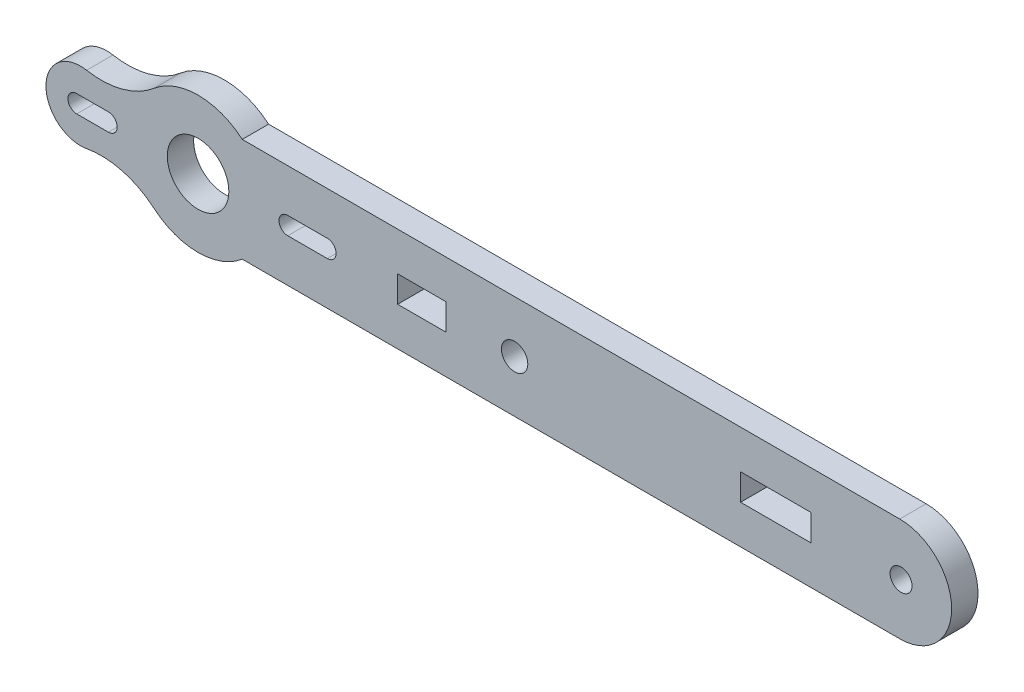
SolidWorks part; units mm, degrees
ref_plane "Plan de face" through (0, 0, 0) normal (0, 0, 1) x (1, 0, 0)
ref_plane "Plan de dessus" through (0, 0, 0) normal (0, 1, 0) x (1, 0, 0)
ref_plane "Plan de droite" through (0, 0, 0) normal (1, 0, 0) x (0, 0, -1)
sketch "Esquisse2" plane through (0, 0, 0) normal (0, 0, 1) x (1, 0, 0)
  line L0 (-102.9894, 7.8317) -> (0.0106, 7.8317) construction
  line L1 (0, 0) -> (-103, 0) construction
  line L2 (0, 0) -> (0, 15.5) construction
  line L3 (0, 15.5) -> (-103, 15.5) construction
  line L4 (-103, 0) -> (-103, 15.5) construction
  line L5 (-103, 7.75) -> (0, 7.75) construction
  line L6 (-80.6748, 13.65) -> (-5.9, 13.65)
  line L7 (-80.6748, 1.85) -> (-5.9, 1.85)
  line L8 (-75.5, 7.75) -> (-71, 7.75) construction
  line L9 (-24, 9.25) -> (-16, 9.25)
  line L10 (-24, 9.25) -> (-24, 6.25)
  line L11 (-24, 6.25) -> (-16, 6.25)
  line L12 (-16, 9.25) -> (-16, 6.25)
  line L13 (-63, 9.25) -> (-57.5, 9.25)
  line L14 (-63, 9.25) -> (-63, 6.25)
  line L15 (-63, 6.25) -> (-57.5, 6.25)
  line L16 (-57.5, 9.25) -> (-57.5, 6.25)
  line L17 (-75.5, 8.75) -> (-71, 8.75)
  line L18 (-75.5, 6.75) -> (-71, 6.75)
  line L19 (-99.5, 7.75) -> (-95.9, 7.75) construction
  line L20 (-99.5, 8.75) -> (-95.9, 8.75)
  line L21 (-99.5, 6.75) -> (-95.9, 6.75)
  circle A0 centre (-85.7, 7.75) radius 3.5
  arc A1 (-5.9, 1.85) -> (-5.9, 13.65) centre (-5.9, 7.75) ccw
  circle A2 centre (-5.75, 7.75) radius 1.25
  circle A3 centre (-49.7, 7.75) radius 1.5
  arc A4 (-75.5, 8.75) -> (-75.5, 6.75) centre (-75.5, 7.75) ccw
  arc A5 (-71, 6.75) -> (-71, 8.75) centre (-71, 7.75) ccw
  arc A6 (-90.7075, 1.835) -> (-80.6748, 1.85) centre (-85.7, 7.75) ccw
  arc A7 (-98.3744, 11.612) -> (-98.375, 3.8879) centre (-99.075, 7.75) ccw
  arc A8 (-90.7082, 13.6644) -> (-98.3744, 11.612) centre (-96.7153, 20.7583) cw
  arc A9 (-90.7075, 1.835) -> (-98.375, 3.8879) centre (-96.7165, -5.263) ccw
  arc A10 (-80.6748, 13.65) -> (-90.7082, 13.6644) centre (-85.7, 7.75) ccw
  arc A11 (-99.5, 8.75) -> (-99.5, 6.75) centre (-99.5, 7.75) ccw
  arc A12 (-95.9, 6.75) -> (-95.9, 8.75) centre (-95.9, 7.75) ccw
  point P31 (-73.25, 7.75)
  point P36 (-76.5, 7.75)
  point P37 (-70, 7.75)
  point P38 (-97.7, 7.75)
  point P52 (-100.5, 7.75)
  point P53 (-94.9, 7.75)
  dimension "D4" = 7
  dimension "D7" = 11.8
  dimension "D8" = 2.5
  dimension "D14" = 3
  dimension "D15" = 41.2
  dimension "D23" = 15.5
  dimension "D24" = 7.85
  dimension "D25" = 9.2956
  dimension "D26" = 9.3
  dimension "D28" = 5.6
  dimension "D30" = 2.5
  dimension "D1" = 103
  dimension "D2" = 15.5
  dimension "D3" = 103
  dimension "D5" = 13.8
  dimension "D6" = 11.8
  dimension "D9" = 4.5
  dimension "D10" = 8
  dimension "D11" = 3
  dimension "D12" = 1.5
  dimension "D13" = 16
  dimension "D16" = 5.5
  dimension "D17" = 3
  dimension "D18" = 33.5
  dimension "D19" = 1.5
  dimension "D20" = 6.5
  dimension "D21" = 2
  dimension "D22" = 7
  dimension "D27" = 2
  dimension "D29" = 1
base flange "Tôle de base pliée1" sketch "Esquisse2" thickness 3 reverse thickness direction no parameters "D1"=1.5
sketch "Lignes de pliage1" [suppressed] plane through (0, 0, 0) normal (0, 1, 0) x (1, 0, 0)
sketch "Cube de visualisation1" [suppressed] plane through (0, 0, 0) normal (0, 1, 0) x (1, 0, 0)
sheet metal parameters "Tôlerie1" thickness 3 parameters "D1"=1.5
flat pattern "Etat déplié1" [suppressed]
sketch "Lignes de pliage2" plane through (0, 0, 0) normal (0, 1, 0) x (1, 0, 0)
sketch3d "Cube de visualisation2" [suppressed]
  line L0 (-17.1119, -8.1489, 0) -> (85.8352, -5.7615, 0) construction
  line L1 (-17.4712, 7.3468, 0) -> (85.4758, 9.7341, 0) construction
  line L2 (-17.1119, -8.1489, 0) -> (-17.4712, 7.3468, 0) construction
  line L3 (85.8352, -5.7615, 0) -> (85.4758, 9.7341, 0) construction
